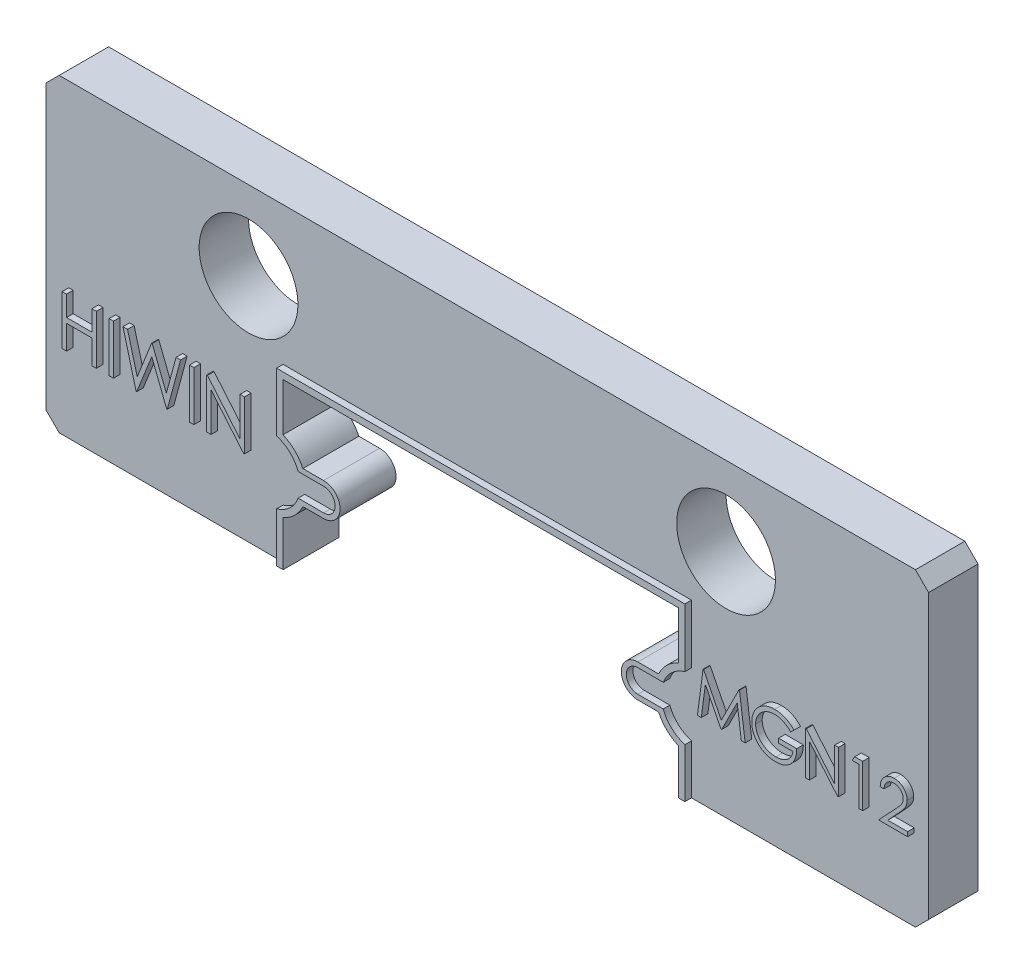
SolidWorks part; units mm, degrees
material "EPDM 60 Durometer"
ref_plane "Front Plane" through (0, 0, 0) normal (0, 0, 1) x (1, 0, 0)
ref_plane "Top Plane" through (0, 0, 0) normal (0, 1, 0) x (1, 0, 0)
ref_plane "Right Plane" through (0, 0, 0) normal (1, 0, 0) x (0, 0, -1)
sketch "Sketch1" plane through (0, 0, 0) normal (0, 0, 1) x (1, 0, 0)
  line L0 (0, 4.7) -> (0, -4.7) construction
  line L19 (-6, -4.7) -> (-13, -4.7)
  line L20 (-13, -4.7) -> (-13.4, -4.3)
  line L21 (-13.4, -4.3) -> (-13.4, 4.3)
  line L22 (-13.4, 4.3) -> (-13, 4.7)
  line L24 (-6, -4.7) -> (-6, -3.3289)
  line L25 (-6, -1.1511) -> (-6, 0.3)
  line L33 (-4.77, -2.74) -> (-5.4001, -2.74)
  line L34 (-4.77, -1.74) -> (-5.4001, -1.74)
  line L35 (-13, 4.7) -> (13, 4.7)
  line L36 (-6, 0.3) -> (6, 0.3)
  line L37 (6, -1.1511) -> (6, 0.3)
  line L38 (4.77, -1.74) -> (5.4001, -1.74)
  line L39 (4.77, -2.74) -> (5.4001, -2.74)
  line L40 (6, -4.7) -> (6, -3.3289)
  line L41 (6, -4.7) -> (13, -4.7)
  line L42 (13, -4.7) -> (13.4, -4.3)
  line L43 (13.4, -4.3) -> (13.4, 4.3)
  line L44 (13.4, 4.3) -> (13, 4.7)
  circle A6 centre (-6.48, -2.24) radius 1.19 construction
  circle A7 centre (-4.77, -2.24) radius 0.5 construction
  arc A10 (-6, -3.3289) -> (-5.4001, -2.74) centre (-6.48, -2.24) ccw
  arc A11 (-5.4001, -1.74) -> (-6, -1.1511) centre (-6.48, -2.24) ccw
  arc A12 (-4.77, -2.74) -> (-4.77, -1.74) centre (-4.77, -2.24) ccw
  arc A13 (5.4001, -1.74) -> (6, -1.1511) centre (6.48, -2.24) cw
  arc A14 (4.77, -2.74) -> (4.77, -1.74) centre (4.77, -2.24) cw
  arc A15 (6, -3.3289) -> (5.4001, -2.74) centre (6.48, -2.24) cw
  point P3 (0, 0)
  point P17 (0, 0.3)
  point P26 (0, 0.3)
  dimension "D10" = 1
  dimension "D12" = 2.54
  dimension "D8" = 9.4
  dimension "D9" = 2.38
  dimension "D11" = 2.54
  dimension "D13" = 4.77
  dimension "D14" = 6.48
  dimension "D1" = 0.4
  dimension "D2" = 0.4
  dimension "D3" = 6
  dimension "D4" = 6
  dimension "D5" = 13.4
  dimension "D6" = 0.4
  dimension "D7" = 5
extrude "Boss-Extrude1" add sketch "Sketch1" against normal blind 1.5 contours L39 | A14 L38 L22 L21 L20 L19 L24 L25 L39 region at (0, 0.6272, 0)
sketch "Sketch2" plane through (0, 0, 0) normal (0, 0, 1) x (1, 0, 0)
  line L1 (-6, -1.1511) -> (-6, 0.3) construction
  line L2 (-6, -4.7) -> (-13, -4.7) construction
  line L3 (6, -1.1511) -> (6, 0.3) construction
  line L4 (6, -4.7) -> (13, -4.7) construction
  circle A0 centre (-7.25, 2.3) radius 1.5
  circle A1 centre (7.25, 2.3) radius 1.5
  dimension "D1" = 1.25
  dimension "D2" = 7
  dimension "D3" = 1.25
  dimension "D4" = 7
extrude "Cut-Extrude1" cut sketch "Sketch2" against normal through all
sketch "Sketch3" plane through (0, 0, 0) normal (0, 0, 1) x (1, 0, 0)
  line L0 (-6.48, -2.24) -> (-13.4, -2.24) construction
  line L1 (-13.4, -4.3) -> (-13.4, 4.3) construction
  line L2 (6.48, -2.24) -> (13.4, -2.24) construction
  line L3 (13.4, -4.3) -> (13.4, 4.3) construction
  text T0 "HIWIN" font "Century Gothic" height 1.5
  text T1 "MGN12" font "Century Gothic" height 1.3
extrude "Boss-Extrude2" add sketch "Sketch3" along normal blind 0.2
sketch "Sketch4" plane through (0, 0, 0) normal (0, 0, 1) x (1, 0, 0)
  line L0 (-6.2, -4.7) -> (-6.2, -3.2)
  line L1 (-6, -4.7) -> (-13, -4.7) construction
  line L2 (-6, -4.7) -> (-6, -3.3289) construction
  line L3 (-6.2, -4.7) -> (-6, -4.7)
  line L4 (-6, -4.7) -> (-6, -3.3289)
  line L5 (-5.4001, -2.74) -> (-4.77, -2.74)
  line L6 (-4.77, -1.74) -> (-5.4001, -1.74)
  line L7 (-6, -1.1511) -> (-6, 0.3) construction
  line L8 (-6, -1.1511) -> (-6, 0.3)
  line L9 (-6.2, 0.5) -> (6.2, 0.5)
  line L10 (-6.2, 0.5) -> (-6.2, -1.28)
  line L11 (-6, 0.3) -> (6, 0.3) construction
  line L12 (6, -1.1511) -> (6, 0.3)
  line L13 (-6, 0.3) -> (6, 0.3)
  line L14 (0, 0.3) -> (0, -4.7) construction
  line L15 (-4.77, -2.59) -> (-5.5433, -2.59)
  line L16 (-4.77, -1.89) -> (-5.5433, -1.89)
  line L17 (6.2, 0.5) -> (6.2, -1.28)
  line L18 (4.77, -1.74) -> (5.4001, -1.74)
  line L19 (4.77, -1.89) -> (5.5433, -1.89)
  line L20 (4.77, -2.59) -> (5.5433, -2.59)
  line L21 (5.4001, -2.74) -> (4.77, -2.74)
  line L22 (6.2, -4.7) -> (6.2, -3.2)
  line L23 (6, -4.7) -> (6, -3.3289)
  line L24 (6.2, -4.7) -> (6, -4.7)
  circle A0 centre (-6.48, -2.24) radius 1 construction
  circle A1 centre (-4.77, -2.24) radius 0.35 construction
  arc A2 (-6, -3.3289) -> (-5.4001, -2.74) centre (-6.48, -2.24) ccw
  arc A3 (-6, -3.3289) -> (-5.4001, -2.74) centre (-6.48, -2.24) ccw construction
  arc A4 (-4.77, -2.74) -> (-4.77, -1.74) centre (-4.77, -2.24) ccw
  arc A5 (-4.77, -2.74) -> (-4.77, -1.74) centre (-4.77, -2.24) ccw construction
  arc A6 (-5.4001, -1.74) -> (-6, -1.1511) centre (-6.48, -2.24) ccw
  arc A7 (-6.2, -3.2) -> (-5.5433, -2.59) centre (-6.48, -2.24) ccw
  arc A8 (-5.5433, -1.89) -> (-6.2, -1.28) centre (-6.48, -2.24) ccw
  arc A9 (-4.77, -2.59) -> (-4.77, -1.89) centre (-4.77, -2.24) ccw
  arc A10 (5.4001, -1.74) -> (6, -1.1511) centre (6.48, -2.24) cw
  arc A11 (5.5433, -1.89) -> (6.2, -1.28) centre (6.48, -2.24) cw
  arc A12 (4.77, -2.59) -> (4.77, -1.89) centre (4.77, -2.24) cw
  arc A13 (4.77, -2.74) -> (4.77, -1.74) centre (4.77, -2.24) cw
  arc A14 (6, -3.3289) -> (5.4001, -2.74) centre (6.48, -2.24) cw
  arc A15 (6.2, -3.2) -> (5.5433, -2.59) centre (6.48, -2.24) cw
  point P51 (0, 0.5)
  dimension "D1" = 2
  dimension "D2" = 0.7
  dimension "D3" = 0.2
  dimension "D4" = 0.2
  dimension "D5" = 0.2
extrude "Boss-Extrude3" add sketch "Sketch4" along normal blind 0.2
